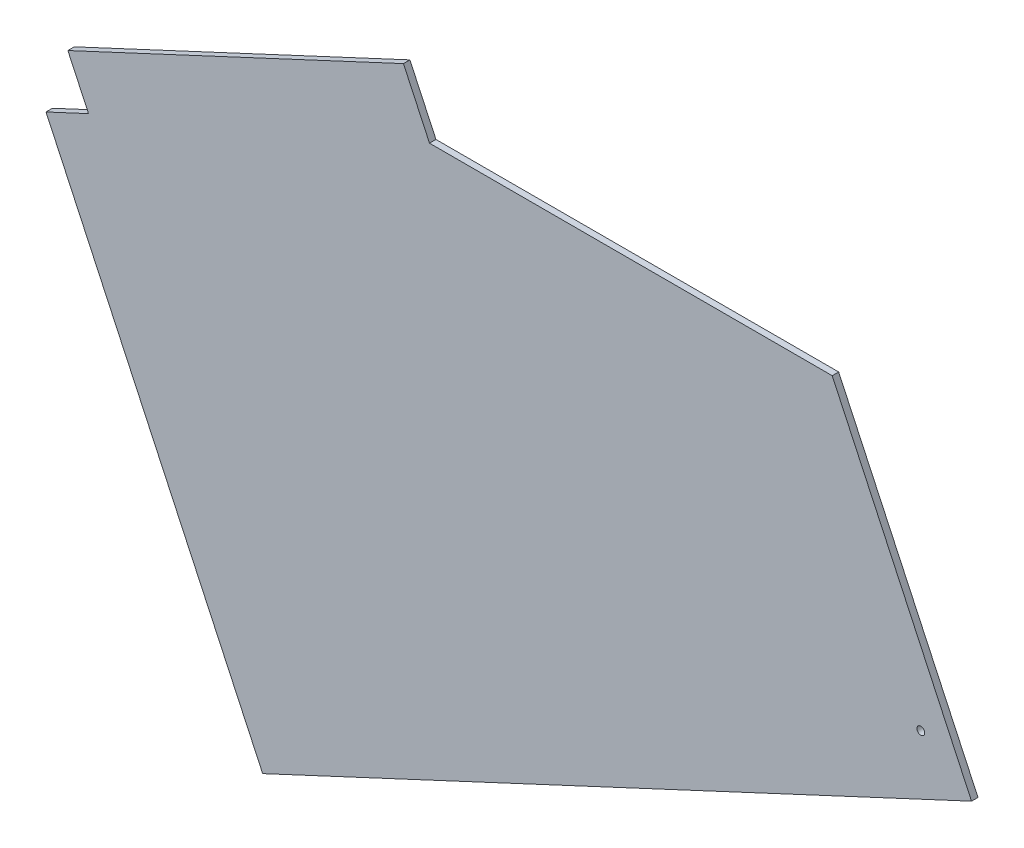
SolidWorks part; units mm, degrees
ref_plane "Front Plane" through (0, 0, 0) normal (0, 0, 1) x (1, 0, 0)
ref_plane "Top Plane" through (0, 0, 0) normal (0, 1, 0) x (1, 0, 0)
ref_plane "Right Plane" through (0, 0, 0) normal (1, 0, 0) x (0, 0, -1)
sketch "Sketch1" plane through (0, 0, 0) normal (0, 0, 1) x (1, 0, 0)
  line L0 (327.4362, 0.0035) -> (121.4984, 0.0035)
  line L1 (121.4984, 0.0035) -> (108.169, 28.5884)
  line L2 (108.169, 28.5884) -> (-63.4467, -51.4373)
  line L3 (-63.4467, -51.4373) -> (57.9293, -311.7289) construction
  line L4 (57.9293, -311.7289) -> (398.701, -152.8244)
  line L5 (271.5352, 119.8836) -> (277.3251, 107.4672) construction
  line L6 (190.5834, 136.311) -> (-12.0446, 41.824) construction
  line L7 (-63.4467, -51.4373) -> (255.5737, 97.3243) construction
  line L8 (398.701, -152.8244) -> (327.4362, 0.0035)
  line L9 (57.9293, -311.7289) -> (36.1779, -321.8717)
  line L10 (36.1779, -321.8717) -> (-74.6326, -84.2378)
  line L11 (50.7481, 0) -> (323.7481, 0) construction
  line L12 (-74.6326, -84.2378) -> (-52.8812, -74.095)
  line L13 (-90.9879, -49.1637) -> (-85.1981, -61.5801) construction
  line L14 (-52.8812, -74.095) -> (-63.4467, -51.4373)
  circle A0 centre (162.7613, -40.6644) radius 32.5 construction
  circle A1 centre (336.0773, -108.8767) radius 32.5 construction
  circle A2 centre (90.1802, -40.6644) radius 32.5 construction
  circle A3 centre (232.5481, -40.6644) radius 32.5 construction
  circle A4 centre (207.2768, 100.5118) radius 39.5 construction
  arc A5 (-3.3339, 41.4724) -> (-17.3744, 34.9252) centre (-8.0297, 33.2141) ccw construction
  circle A6 centre (304.5287, -40.6644) radius 32.5 construction
  circle A7 centre (254.9584, -108.8767) radius 32.5 construction
  circle A8 centre (179.3206, -108.8767) radius 32.5 construction
  circle A9 centre (101.4264, -108.8767) radius 32.5 construction
  circle A10 centre (270.383, -163.8108) radius 32.5 construction
  circle A11 centre (372.7594, -134.5783) radius 2
  dimension "D2" = 65
  dimension "D3" = 65
  dimension "D5" = 4
  dimension "D1" = 350
  dimension "D4" = 25
  dimension "24.5/2" = 15.8
  dimension "D6" = 27.5
extrude "Boss-Extrude1" add sketch "Sketch1" along normal up to surface (3.3 mm away)
